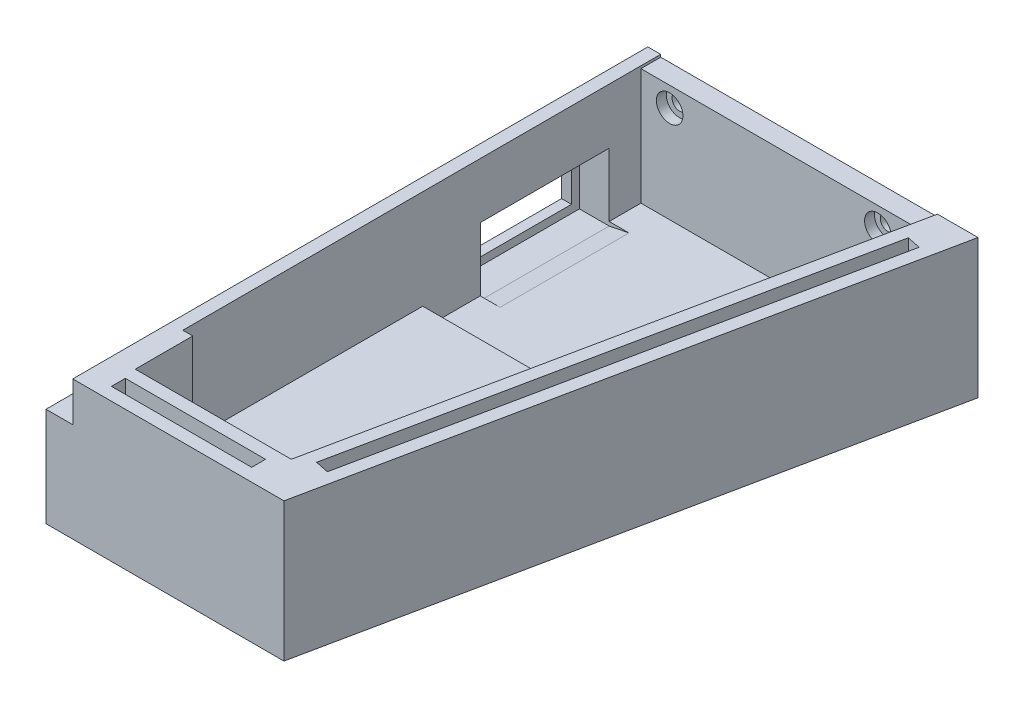
SolidWorks part; units mm, degrees
ref_plane "Front Plane" through (0, 0, 0) normal (1, 0, 0) x (0, 1, 0)
ref_plane "Top Plane" through (0, 0, 0) normal (0, 0, 1) x (0, 1, 0)
ref_plane "Right Plane" through (0, 0, 0) normal (0, 1, 0) x (-1, 0, 0)
sketch "Sketch1" plane through (0, 0, 0) normal (0, 1, 0) x (-1, 0, 0)
  line L0 (-13.4363, 2.5951) -> (16.5637, 147.5951)
  line L1 (-13.4363, -4.9049) -> (-8.4363, -4.9049)
  line L2 (-13.4363, -4.9049) -> (-13.4363, 2.5951)
  line L3 (-13.4363, 2.5951) -> (-8.4363, 2.5951)
  line L4 (-8.4363, -4.9049) -> (-8.4363, 2.5951)
  line L13 (-13.4363, 2.5951) -> (16.5637, 147.5951)
  line L14 (-13.4363, 2.5951) -> (-3.6437, 0.569)
  line L15 (-13.4363, 2.5951) -> (66.5637, 2.5951) construction
  line L16 (-13.4363, 2.5951) -> (-13.4363, 137.5951) construction
  line L17 (-13.4363, 137.5951) -> (66.5637, 137.5951) construction
  line L18 (66.5637, 2.5951) -> (66.5637, 137.5951) construction
  line L19 (66.5637, 137.5951) -> (16.5637, 137.5951)
  line L20 (66.5637, 137.5951) -> (66.5637, 147.5951)
  line L21 (66.5637, 147.5951) -> (16.5637, 147.5951)
  line L22 (16.5637, 137.5951) -> (16.5637, 147.5951)
  line L23 (16.5637, 147.5951) -> (26.3563, 145.569)
  line L24 (-3.6437, 0.569) -> (26.3563, 145.569)
  line L25 (-8.4363, 2.5951) -> (-3.2246, 2.5951)
  line L27 (-3.2246, 2.5951) -> (66.5637, 2.5951)
  line L28 (-3.2246, 2.5951) -> (-3.2246, 7.5951)
  line L29 (-3.2246, 7.5951) -> (66.5637, 7.5951)
  line L30 (66.5637, 2.5951) -> (66.5637, 7.5951)
  line L35 (66.5637, 147.5951) -> (76.5637, 147.5951)
  line L36 (66.5637, 147.5951) -> (66.5637, 2.5951)
  line L37 (66.5637, 2.5951) -> (76.5637, 2.5951)
  line L38 (76.5637, 147.5951) -> (76.5637, 2.5951)
  dimension "D1" = 7.5
  dimension "D3" = 135
  dimension "D4" = 80
  dimension "D5" = 10
  dimension "D7" = 10
  dimension "D9" = 5
  dimension "D8" = 10
  dimension "D6" = 50
extrude "Boss-Extrude1" add sketch "Sketch1" along normal blind 35 contours L24 L19 L20 L21 L23 | L19 L24 L23 L22 | L28 L29 L24 L19 L22 L0 L3 L25 | L38 L35 L20 L36 L30 L37 | L29 L28 L24 | L27 L30 L29 L24 region at (-5.7274, 0, 70.7433) region at (-20.91, 0, 142.2574) region at (-45.5816, 0, 142.6608) region at (-71.5637, 0, 75.0951) region at (2.8797, 0, 5.9284) region at (-31.9275, 0, 5.0889)
sketch "Sketch3" plane through (0, 0, 0) normal (0, -1, 0) x (1, 0, 0)
  line L0 (-76.5637, 147.5951) -> (-16.5637, 147.5951)
  line L1 (-16.5637, 147.5951) -> (13.4363, 2.5951)
  line L2 (13.4363, 2.5951) -> (-76.5637, 2.5951)
  line L3 (-76.5637, 2.5951) -> (-76.5637, 147.5951)
extrude "Boss-Extrude2" add sketch "Sketch3" against normal blind 10
sketch "Sketch4" plane through (0, 35, 0) normal (0, 1, 0) x (-1, 0, 0)
  line L0 (24.7065, 137.5951) -> (-2.1901, 7.5951)
  line L1 (24.7065, 137.5951) -> (66.5637, 137.5951)
  line L2 (24.7065, 137.5951) -> (24.7065, 147.5951)
  line L3 (24.7065, 147.5951) -> (66.5637, 147.5951)
  line L4 (66.5637, 137.5951) -> (66.5637, 147.5951)
  line L5 (24.7065, 137.5951) -> (14.9139, 139.6211)
  line L6 (-2.1901, 7.5951) -> (-11.9827, 9.6211)
  line L7 (14.9139, 139.6211) -> (-11.9827, 9.6211)
  line L9 (20.8654, 135.071) -> (-4.7142, 11.4361)
  line L10 (-4.7142, 11.4361) -> (-8.1416, 12.1453)
  line L11 (17.438, 135.7801) -> (-8.1416, 12.1453)
  line L12 (20.8654, 135.071) -> (17.438, 135.7801)
  line L13 (27.9565, 140.8451) -> (27.9565, 144.3451)
  line L14 (27.9565, 144.3451) -> (63.3137, 144.3451)
  line L15 (63.3137, 140.8451) -> (63.3137, 144.3451)
  line L16 (27.9565, 140.8451) -> (63.3137, 140.8451)
  line L17 (76.5637, 147.5951) -> (16.5637, 147.5951) construction
  line L18 (17.438, 135.7801) -> (19.8825, 147.5951)
  line L20 (20.8654, 135.071) -> (23.4566, 147.5951)
  line L21 (23.4566, 147.5951) -> (19.8825, 147.5951)
  line L22 (27.9565, 144.3451) -> (19.2101, 144.3451)
  line L23 (19.2101, 144.3451) -> (18.4859, 140.8451)
  line L24 (18.4859, 140.8451) -> (27.9565, 140.8451)
  line L25 (-13.4363, 2.5951) -> (16.5637, 147.5951) construction
  dimension "D1" = 3.25
extrude "Cut-Extrude1" cut sketch "Sketch4" against normal blind 10 contours L9 L12 L11 L10 | L13 L16 L15 L14 region at (-45.6351, 35, 142.5951) region at (-6.3619, 35, 73.6081)
sketch "Sketch5" plane through (0, 35, -3.0299) normal (0, -1, 0) x (1, 0, 0)
  line L5 (13.4363, 5.625) -> (-76.5637, 5.625) construction
  line L6 (-66.5637, 10.625) -> (2.1901, 10.625)
  line L7 (-66.5637, 10.625) -> (-66.5637, 5.625)
  line L8 (-66.5637, 5.625) -> (2.1901, 5.625)
  line L9 (2.1901, 10.625) -> (2.1901, 5.625)
  line L10 (2.1901, 10.625) -> (3.2246, 5.625)
  line L11 (2.1901, 10.625) -> (-24.7065, 140.625) construction
  line L12 (3.2246, 5.625) -> (2.1901, 5.625)
  line M9 (-66.5637, 10.625) -> (2.1901, 10.625)
  line M14 (13.4363, 5.625) -> (-76.5637, 5.625)
extrude "Cut-Extrude2" cut sketch "Sketch5" along normal blind 0.625 contours L9 L10 M14 | L9 L7 M9 M14 region at (-32.1868, 35, 5.0951) region at (2.5349, 35, 4.2617)
sketch "Sketch6" plane through (0, 0, 7.5951) normal (0, 0, 1) x (1, 0, 0)
  line L1 (-66.5637, 34.375) -> (-59.3137, 34.375) construction
  line L2 (-66.5637, 34.375) -> (-66.5637, 29.375) construction
  line L3 (-66.5637, 29.375) -> (-59.3137, 29.375) construction
  line L4 (-59.3137, 34.375) -> (-59.3137, 29.375) construction
  circle A0 centre (-59.3137, 29.375) radius 1.9
  dimension "D3" = 3.8
  dimension "D1" = 7.25
extrude "Cut-Extrude3" cut sketch "Sketch6" against normal up to next
sketch "Sketch7" plane through (0, 0, 7.5951) normal (0, 0, 1) x (1, 0, 0)
  circle A0 centre (-59.3137, 29.375) radius 3.35
  dimension "D1" = 6.7
extrude "Cut-Extrude4" cut sketch "Sketch7" against normal blind 2.5
pattern_linear "LPattern1" count 2 spacing 52.5 along (1, 0, 0) of "Cut-Extrude4", "Cut-Extrude3"
sketch "Sketch8" plane through (0, 35, 0) normal (0, 1, 0) x (-1, 0, 0)
  line L0 (76.5637, 147.5951) -> (16.5637, 147.5951) construction
  line L1 (66.5637, 2.5951) -> (69.8137, 2.5951)
  line L2 (66.5637, 2.5951) -> (66.5637, 147.5951)
  line L3 (66.5637, 147.5951) -> (69.8137, 147.5951)
  line L4 (69.8137, 2.5951) -> (69.8137, 147.5951)
  line L5 (66.5637, 2.5951) -> (76.5637, 2.5951) construction
  line L6 (76.5637, 147.5951) -> (73.3137, 147.5951)
  line L7 (76.5637, 147.5951) -> (76.5637, 2.5951)
  line L8 (76.5637, 2.5951) -> (73.3137, 2.5951)
  line L9 (73.3137, 147.5951) -> (73.3137, 2.5951)
  line L11 (73.3137, 2.5951) -> (69.8137, 2.5951)
  line L12 (73.3137, 2.5951) -> (73.3137, 147.5951)
  line L13 (73.3137, 147.5951) -> (69.8137, 147.5951)
  line L14 (69.8137, 2.5951) -> (69.8137, 147.5951)
  line M8 (66.5637, 2.5951) -> (76.5637, 2.5951)
  line M9 (76.5637, 2.5951) -> (76.5637, 147.5951)
  line M10 (76.5637, 147.5951) -> (16.5637, 147.5951)
  dimension "D1" = 3.25
  dimension "D2" = 3.25
extrude "Cut-Extrude5" cut sketch "Sketch8" against normal blind 10 contours L9 L4 M10 M8 | L9 M10 M8 M9 region at (-71.5637, 35, 75.0951) region at (-74.9387, 35, 75.0951)
sketch "Sketch10" plane through (0, 10, 0) normal (0, 1, 0) x (-1, 0, 0)
  line L9 (66.5637, 7.5951) -> (-2.1901, 7.5951) construction
  line L14 (66.5637, 7.5951) -> (26.5637, 7.5951)
  line L15 (66.5637, 7.5951) -> (66.5637, 62.5951)
  line L16 (66.5637, 62.5951) -> (26.5637, 62.5951)
  line L17 (26.5637, 7.5951) -> (26.5637, 62.5951)
  line L18 (66.5637, 7.5951) -> (66.5637, 2.5951) construction
  line L19 (26.5637, 62.5951) -> (15.1843, 7.5951)
  line L20 (15.1843, 7.5951) -> (26.5637, 7.5951)
  line L21 (-3.2246, 2.5951) -> (24.7065, 137.5951) construction
  line M16 (-2.1901, 7.5951) -> (66.5637, 7.5951)
  line M17 (66.5637, 7.5951) -> (66.5637, 137.5951)
  dimension "D1" = 40
  dimension "D2" = 55
extrude "Cut-Extrude6" cut sketch "Sketch10" against normal blind 5 contours L17 L19 M16 | L17 L16 M16 M17 region at (-46.5637, 10, 35.0951) region at (-22.7706, 10, 25.9284)
sketch "Sketch9" plane through (-76.5637, 0, 0) normal (-1, 0, 0) x (0, -1, 0)
  line L1 (0, 2.5951) -> (-6, 2.5951) construction
  line L2 (0, 2.5951) -> (0, 17.5951) construction
  line L3 (0, 17.5951) -> (-6, 17.5951) construction
  line L4 (-6, 2.5951) -> (-6, 17.5951) construction
  line L5 (-6, 17.5951) -> (-19, 17.5951)
  line L6 (-6, 17.5951) -> (-6, 46.0951)
  line L7 (-6, 46.0951) -> (-19, 46.0951)
  line L8 (-19, 17.5951) -> (-19, 46.0951)
  point P8 (0, 2.5951)
  point P10 (6, 2.5951)
  point P11 (6, 17.5951)
  dimension "D3" = 28.5
  dimension "D4" = 13
extrude "Cut-Extrude7" cut sketch "Sketch9" against normal up to next
sketch "Sketch11" plane through (-66.5637, 0, 0) normal (1, 0, 0) x (0, 1, 0)
  line L0 (4, 48.0951) -> (4, 15.5951)
  line L1 (6, 46.0951) -> (19, 46.0951)
  line L2 (6, 46.0951) -> (6, 17.5951)
  line L3 (6, 17.5951) -> (19, 17.5951)
  line L4 (19, 46.0951) -> (19, 17.5951)
  line L5 (4, 15.5951) -> (21, 15.5951)
  line L6 (21, 48.0951) -> (21, 15.5951)
  line L7 (4, 48.0951) -> (21, 48.0951)
  dimension "D1" = 2
extrude "Cut-Extrude8" cut sketch "Sketch11" against normal blind 7.5
chamfer "Chamfer1" distance 1 distance2 5 1 edges at (-66.5637, 5, 31.8451) first distance on face at (-66.5637, 4.5, 31.8451)
sketch "Sketch14" plane through (-66.5637, 0, 0) normal (1, 0, 0) x (0, 1, 0)
  line L0 (10, 62.5951) -> (10, 137.5951) construction
  line L1 (35, 137.5951) -> (10, 137.5951)
  line L2 (35, 137.5951) -> (35, 123.0951)
  line L3 (35, 123.0951) -> (10, 123.0951)
  line L4 (10, 137.5951) -> (10, 123.0951)
  dimension "D1" = 14.5
extrude "Boss-Extrude3" add sketch "Sketch14" along normal blind 2.5
sketch "Sketch13" plane through (-69.8137, 0, 0) normal (-1, 0, 0) x (0, -1, 0)
  line L1 (-25, 147.5951) -> (-30, 147.5951) construction
  line L2 (-25, 147.5951) -> (-25, 130.3451) construction
  line L3 (-25, 130.3451) -> (-30, 130.3451) construction
  line L4 (-30, 147.5951) -> (-30, 130.3451) construction
  circle A0 centre (-30, 130.3451) radius 2.4
  dimension "D3" = 4.8
  dimension "D1" = 17.25
extrude "Cut-Extrude9" cut sketch "Sketch13" against normal blind 3.8
equation "\"whitekey_cutout_length\"= 101.5"
equation "\"whitekey_spacing\"=1.25"
equation "\"key_mount_recess_length\"=50"
equation "\"key_mount_recess_height\"=12.5"
equation "\"key_mount_recess_depth\"=1.5"
equation "\"wall_thickness\"=10"
equation "\"guide_brace_height\"=20"
equation "\"guide_brace_thickness\"=2"
equation "\"dowel_recess_depth\"=10"
equation "\"dowel_recess_offset\"=3.25"
equation "\"dowel_insert_tolerance\"=0.1"
equation "\"base_mount_height\"=40"
equation "\"base_rear_length\"=80"
equation "\"base_front_length\"=111.5"
equation "\"screw_hole_wall_offset\"=7.25"
equation "\"screw_hole_edge_inset\"=\"dowel_recess_depth\"/2"
equation "\"screw_hole_diameter\"=3.8"
equation "\"screw_head_hole_diameter\"=6.7"
equation "\"screw_nut_hole_side_len\"=3.5"
equation "\"screw_nut_recess_offset\"=0.35"
equation "\"screw_head_and_nut_recess_depth\"=2.5"
equation "\"screw_shaft_diameter\"=3.5"
equation "\"switch_board_width\"=30"
equation "\"switch_board_thickness\"=1.6"
equation "\"switch_board_wall_offset\"=11.5"
equation "\"heatset_insert_hole_diameter\"=4.8"
equation "\"heatset_insert_hole_depth\"=3.8"
equation "\"front_rear_panel_width\"=23.75"
equation "\"front_panel_height\"=24"
equation "\"front_rear_panel_recess_depth\"=5"
equation "\"rod_diameter\"=5"
equation "\"rod_head_diameter\"=8"
equation "\"rod_length_adj\"=0.5"
equation "\"rod_insert_length\"=2.8"
equation "\"switch_black_key_mount_height\"=8"
equation "\"switch_white_key_mount_height\"=3"
equation "\"side_panel_depth\"=35"
equation "\"D5@Sketch1\"=\"wall_thickness\""
equation "\"D7@Sketch1\"=\"wall_thickness\""
equation "\"D8@Sketch1\"=\"wall_thickness\""
equation "\"D9@Sketch1\"=\"wall_thickness\"/2"
equation "\"D2@Sketch1\"=\"wall_thickness\"/2"
equation "\"D1@Sketch1\"=\"wall_thickness\"*0.75"
equation "\"D3@Sketch1\"=\"interface_panel_height\""
equation "\"D4@Sketch1\"=\"base_rear_length\""
equation "\"D1@Boss-Extrude1\"=\"side_panel_depth\""
equation "\"D1@Boss-Extrude2\"=\"wall_thickness\""
equation "\"D1@Sketch4\"=\"dowel_recess_offset\""
equation "\"D1@Cut-Extrude1\"=\"dowel_recess_depth\""
equation "\"D1@Sketch6\"=\"screw_hole_wall_offset\""
equation "\"D2@Sketch6\"=\"screw_hole_edge_inset\""
equation "\"D3@Sketch6\"=\"screw_hole_diameter\""
equation "\"D1@Sketch7\"=\"screw_head_hole_diameter\""
equation "\"D3@LPattern1\"=\"base_rear_length\"-\"wall_thickness\"-\"screw_hole_wall_offset\"*2-3"
equation "\"D1@Sketch8\"=\"dowel_recess_offset\""
equation "\"D2@Sketch8\"=\"dowel_recess_offset\""
equation "\"D1@Cut-Extrude5\"=\"front_rear_panel_recess_depth\"*2"
equation "\"D1@Cut-Extrude2\"=\"whitekey_spacing\"/2"
equation "\"interface_panel_height\"=135"
equation "\"interface_panel_roof_length\"=50"
equation "\"D6@Sketch1\"=\"interface_panel_roof_length\""
equation "\"D2@Sketch9\"=\"wall_thickness\"*0.6"
equation "\"D1@Sketch9\"=\"wall_thickness\"*1.5"
equation "\"D1@Sketch10\"=\"base_rear_length\"/2"
equation "\"D2@Sketch10\"=\"interface_panel_height\"/3+\"wall_thickness\""
equation "\"D1@Cut-Extrude6\"=\"wall_thickness\"/2"
equation "\"D1@Cut-Extrude8\"=\"wall_thickness\"*0.75"
equation "\"D1@Sketch13\"=\"wall_thickness\"+\"screw_hole_wall_offset\""
equation "\"D2@Sketch13\"=\"screw_hole_edge_inset\""
equation "\"D3@Sketch13\"=\"heatset_insert_hole_diameter\""
equation "\"D1@Sketch14\"=\"screw_hole_wall_offset\"*2"
equation "\"D1@Boss-Extrude3\"=\"wall_thickness\"/4"
equation "\"D1@Cut-Extrude9\"=\"heatset_insert_hole_depth\""
